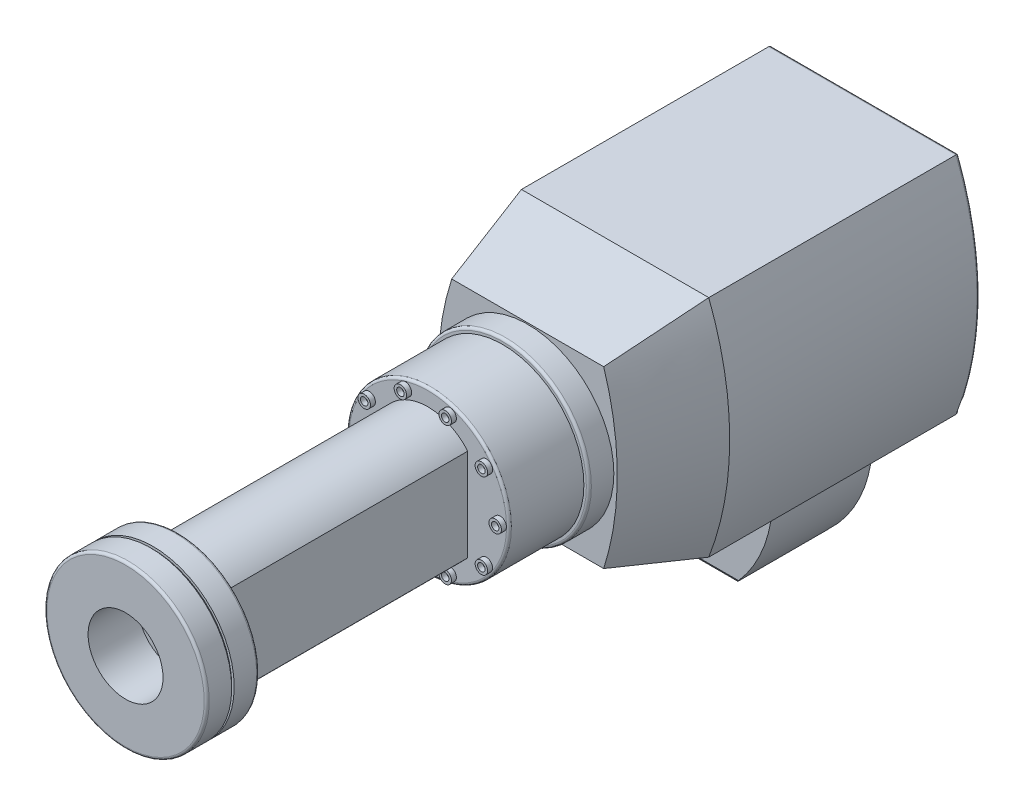
SolidWorks part; units mm, degrees
ref_plane "Front" through (0, 0, 0) normal (0, 0, 1) x (1, 0, 0)
ref_plane "Top" through (0, 0, 0) normal (0, 1, 0) x (1, 0, 0)
ref_plane "Right" through (0, 0, 0) normal (1, 0, 0) x (0, 0, -1)
sketch "Sketch1" plane through (0, 0, 0) normal (0, 0, 1) x (1, 0, 0)
  line L0 (0, 0) -> (0, 45) construction
  line L1 (0, 0) -> (0, -45) construction
  line L2 (-37.5, 45) -> (37.5, 45)
  line L3 (0, 0) -> (39.7129, 0) construction
  line L4 (-37.5, -45) -> (37.5, -45)
  arc A0 (-37.5, 45) -> (-37.5, -45) centre (79.119, 0) ccw
  arc A1 (37.5, 45) -> (37.5, -45) centre (-79.119, 0) cw
  dimension "D3" = 125
  dimension "D1" = 45
  dimension "D2" = 37.5
extrude "Boss-Extrude1" add sketch "Sketch1" along normal blind 100 contours L2 A1 L4 A0
sketch "Sketch2" plane through (0, 0, 100) normal (0, 0, 1) x (1, 0, 0)
  line L2 (-37.5, -45) -> (37.5, -45)
  line L3 (37.5, 45) -> (-37.5, 45)
  line L4 (-37.5, -45) -> (37.5, -45)
  line L5 (37.5, 45) -> (-37.5, 45)
  arc A2 (-37.5, 45) -> (-37.5, -45) centre (79.119, 0) ccw
  arc A3 (37.5, -45) -> (37.5, 45) centre (-79.119, 0) ccw
  arc A4 (-37.5, 45) -> (-37.5, -45) centre (79.119, 0) ccw
  arc A5 (37.5, -45) -> (37.5, 45) centre (-79.119, 0) ccw
  dimension "D1" = 0
ref_plane "Plane1" through (0, 0, 135) normal (0, 0, 1) x (1, 0, 0)
sketch "Sketch3" plane through (0, 0, 135) normal (0, 0, 1) x (1, 0, 0)
  line L4 (30.4255, 35) -> (-30.4255, 35)
  line L5 (-30.4255, -35) -> (30.4255, -35)
  line L6 (30.4255, 35) -> (-30.4255, 35)
  line L7 (-30.4255, -35) -> (30.4255, -35)
  arc A4 (-30.4255, 35) -> (-30.4255, -35) centre (79.119, 0) ccw
  arc A5 (30.4255, -35) -> (30.4255, 35) centre (-79.119, 0) ccw
  arc A6 (-30.4255, 35) -> (-30.4255, -35) centre (79.119, 0) ccw
  arc A7 (30.4255, -35) -> (30.4255, 35) centre (-79.119, 0) ccw
  dimension "D1" = 10
loft "Loft1" add profiles "Sketch2", "Sketch3" connector at (37.5, 45, 100) connector at (30.4255, 35, 135)
sketch "Sketch4" plane through (0, 0, 135) normal (0, 0, 1) x (1, 0, 0)
  circle A0 centre (0, 0) radius 34.5
  dimension "D1" = 69
extrude "Boss-Extrude2" add sketch "Sketch4" along normal blind 10 contours A0
sketch "Sketch5" plane through (0, 0, 145) normal (0, 0, 1) x (1, 0, 0)
  circle A3 centre (0, 0) radius 32.5
  circle A4 centre (0, 0) radius 32.5
  dimension "D1" = 2
extrude "Boss-Extrude3" add sketch "Sketch5" along normal blind 30
sketch "Sketch6" plane through (0, 0, 175) normal (0, 0, 1) x (1, 0, 0)
  line L0 (0, 0) -> (29, 0) construction
  circle A0 centre (29, 0) radius 2.5
  circle A2 centre (29, 0) radius 1.5
  dimension "D2" = 5
  dimension "D1" = 29
  dimension "D3" = 1
extrude "Boss-Extrude4" add sketch "Sketch6" along normal blind 2
pattern_circular "CirPattern2" count 10 over 360 about axis through (0, 0, 175) along (0, 0, 1) of "Boss-Extrude4"
sketch "Sketch7" plane through (0, 0, 175) normal (0, 0, 1) x (1, 0, 0)
  line L0 (0, 0) -> (16, 0) construction
  line L1 (16, 18.5) -> (16, -18.5)
  line L2 (0, 0) -> (0, -10.308) construction
  line L3 (-16, 18.5) -> (-16, -18.5)
  arc A0 (-16, 18.5) -> (16, 18.5) centre (0, 4.8985) cw
  arc A1 (-16, -18.5) -> (16, -18.5) centre (0, -4.8985) ccw
  dimension "D3" = 21
  dimension "D1" = 16
  dimension "D2" = 18.5
extrude "Boss-Extrude5" add sketch "Sketch7" along normal blind 100
sketch "Sketch8" plane through (0, 0, 275) normal (0, 0, 1) x (1, 0, 0)
  circle A0 centre (0, 0) radius 32.5 construction
  circle A1 centre (0, 0) radius 32.5
extrude "Boss-Extrude6" add sketch "Sketch8" along normal blind 10 contours A1
sketch "Sketch9" plane through (0, 0, 285) normal (0, 0, 1) x (1, 0, 0)
  circle A2 centre (0, 0) radius 31.5
  circle A3 centre (0, 0) radius 31.5
  dimension "D1" = 1
extrude "Boss-Extrude7" add sketch "Sketch9" along normal blind 1
sketch "Sketch10" plane through (0, 0, 286) normal (0, 0, 1) x (1, 0, 0)
  circle A0 centre (0, 0) radius 32.5 construction
  circle A1 centre (0, 0) radius 32.5
extrude "Boss-Extrude8" add sketch "Sketch10" along normal blind 10 contours A1
ref_plane "Plane2" through (-37.5, 0, 0) normal (1, 0, 0) x (0, 0, -1)
sketch "Sketch11" plane through (-37.5, 0, 0) normal (1, 0, 0) x (0, 0, -1)
  line L0 (-100, -45) -> (0, -45) construction
  circle A0 centre (-50, -45) radius 42.5
  dimension "D1" = 85
extrude "Boss-Extrude9" add sketch "Sketch11" along normal mid plane 21 contours A0
sketch "Sketch12" plane through (-27, 0, 0) normal (1, 0, 0) x (0, 0, -1)
  line L0 (-50, -45) -> (-50, -77.165) construction
  line L1 (-100, -45) -> (0, -45) construction
  line L2 (-70, -45) -> (-70, -77.165)
  line L3 (-30, -45) -> (-30, -77.165)
  line L4 (-70, -45) -> (-30, -45)
  arc A0 (-70, -77.165) -> (-30, -77.165) centre (-50, -62.4838) ccw
  dimension "D3" = 24.81
  dimension "D1" = 20
  dimension "D2" = 20
extrude "Boss-Extrude10" add sketch "Sketch12" along normal blind 35 contours L4 L3 A0 L2
ref_plane "Plane3" through (0, 0, 50) normal (0, 0, 1) x (1, 0, 0)
sketch "Sketch13" plane through (0, 0, 50) normal (0, 0, 1) x (1, 0, 0)
  line L0 (8, -45) -> (8, -87)
  line L1 (8, -45) -> (33, -45)
  line L2 (-37.5, -45) -> (37.5, -45) construction
  arc A0 (33, -45) -> (8, -87) centre (-21.8393, -40.7981) cw
  dimension "D3" = 55
  dimension "D1" = 42
  dimension "D2" = 25
extrude "Boss-Extrude11" add sketch "Sketch13" along normal mid plane 40 contours L0 A0 L1
sketch "Sketch15" plane through (8, 0, 0) normal (-1, 0, 0) x (0, 0, 1)
  line L2 (70, -87) -> (70, -77.165)
  line L3 (53.807, -87) -> (70, -87)
  line L4 (70, -87) -> (70, -77.165)
  line L5 (53.807, -87) -> (70, -87)
  arc A1 (53.807, -87) -> (70, -77.165) centre (50, -62.4838) ccw
  arc A2 (53.807, -87) -> (70, -77.165) centre (50, -62.4838) ccw
  dimension "D1" = 0
extrude "Cut-Extrude1" cut sketch "Sketch15" against normal blind 40
sketch "Sketch16" plane through (8, 0, 0) normal (-1, 0, 0) x (0, 0, 1)
  line L2 (30, -87) -> (46.193, -87)
  line L3 (30, -77.165) -> (30, -87)
  line L4 (30, -87) -> (46.193, -87)
  line L5 (30, -77.165) -> (30, -87)
  arc A1 (30, -77.165) -> (46.193, -87) centre (50, -62.4838) ccw
  arc A2 (30, -77.165) -> (46.193, -87) centre (50, -62.4838) ccw
  dimension "D1" = 0
extrude "Cut-Extrude2" cut sketch "Sketch16" against normal blind 40
fillet "Fillet1" radius 1 4 edges at (0, -45, 0) (45.881, 0, 0) (0, 45, 0) (-45.881, 0, 0)
fillet "Fillet2" radius 1 2 edges at (-48, -45, 7.5) (-27, -87.5, 50)
fillet "Fillet3" radius 1 2 edges at (32.5, 0, 175) (34.5, 0, 145)
fillet "Fillet4" radius 1 2 edges at (32.5, 0, 296) (32.5, 0, 275)
sketch "Sketch17" plane through (0, 0, 296) normal (0, 0, 1) x (1, 0, 0)
  circle A0 centre (0, 0) radius 15
  dimension "D1" = 30
extrude "Cut-Extrude3" cut sketch "Sketch17" against normal blind 20
sketch "Sketch18" plane through (-48, 0, 0) normal (-1, 0, 0) x (0, 0, 1)
  circle A0 centre (50, -45) radius 15
  dimension "D1" = 30
extrude "Cut-Extrude4" cut sketch "Sketch18" against normal blind 20
